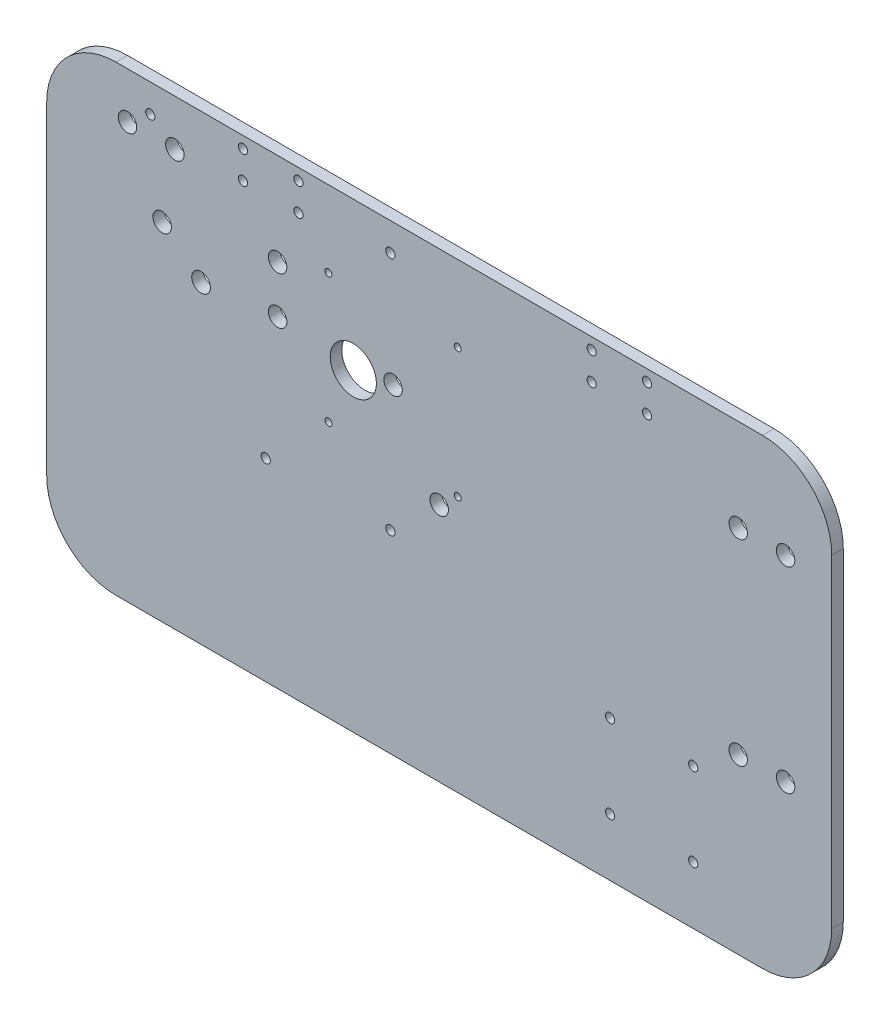
SolidWorks part; units mm, degrees
ref_plane "Alzado" through (0, 0, 0) normal (0, 0, 1) x (1, 0, 0)
ref_plane "Planta" through (0, 0, 0) normal (0, 1, 0) x (1, 0, 0)
ref_plane "Vista lateral" through (0, 0, 0) normal (1, 0, 0) x (0, 0, -1)
sketch "Croquis1" plane through (0, 0, 0) normal (0, 0, 1) x (1, 0, 0)
  line L1 (30, 0) -> (310, 0)
  line L2 (0, 30) -> (0, 170)
  line L3 (30, 200) -> (310, 200)
  line L4 (340, 30) -> (340, 170)
  arc A0 (30, 0) -> (0, 30) centre (30, 30) cw
  arc A1 (310, 0) -> (340, 30) centre (310, 30) ccw
  arc A2 (310, 200) -> (340, 170) centre (310, 170) cw
  arc A3 (0, 170) -> (30, 200) centre (30, 170) cw
  point P7 (0, 0)
  point P12 (340, 200)
  point P15 (0, 200)
  dimension "D3" = 30
  dimension "D1" = 200
  dimension "D2" = 340
extrude "Saliente-Extruir1" add sketch "Croquis1" along normal blind 5
sketch "Croquis2" plane through (0, 0, 5) normal (0, 0, -1) x (-1, 0, 0)
  line L0 (-55.5, 180) -> (-35, 180) construction
  line L2 (-310, 200) -> (-30, 200) construction
  line L3 (0, 170) -> (0, 30) construction
  line L4 (-100, 160) -> (-100, 139.5) construction
  line L5 (-310, 200) -> (-30, 200) construction
  line L6 (-299.5, 160) -> (-320, 160) construction
  line L7 (-340, 30) -> (-340, 170) construction
  line L8 (-320, 75) -> (-299.5, 75) construction
  line L9 (-30, 0) -> (-310, 0) construction
  line L10 (-100, 149.75) -> (-146.5265, 149.75) construction
  circle A0 centre (-55.5, 180) radius 4
  circle A1 centre (-35, 180) radius 4
  circle A2 centre (-100, 160) radius 4
  circle A3 centre (-100, 139.5) radius 4
  circle A4 centre (-299.5, 160) radius 4
  circle A5 centre (-320, 160) radius 4
  circle A6 centre (-320, 75) radius 4
  circle A7 centre (-299.5, 75) radius 4
  circle A8 centre (-150, 139) radius 4
  circle A9 centre (-170, 104) radius 4
  circle A10 centre (-50, 150) radius 4
  dimension "D1" = 8
  dimension "D10" = 40
  dimension "D14" = 8
  dimension "D19" = 8
  dimension "D2" = 20.5
  dimension "D3" = 35
  dimension "D4" = 20
  dimension "D5" = 20.5
  dimension "D6" = 40
  dimension "D7" = 100
  dimension "D8" = 20.5
  dimension "D9" = 20
  dimension "D11" = 20.5
  dimension "D12" = 20
  dimension "D13" = 75
  dimension "D15" = 150
  dimension "D16" = 61
  dimension "D17" = 35
  dimension "D18" = 20
  dimension "D20" = 50
  dimension "D21" = 50
extrude "Cortar-Extruir4" cut sketch "Croquis2" along normal blind 10
sketch "Croquis3" plane through (0, 0, 0) normal (0, 0, -1) x (-1, 0, 0)
  line L0 (-44.85, 187.84) -> (-148.85, 187.84) construction
  line L1 (-148.85, 187.84) -> (-148.85, 83.84) construction
  line L2 (-148.85, 83.84) -> (-94.85, 83.84) construction
  line L3 (-94.85, 83.84) -> (-44.85, 187.84) construction
  line L4 (-310, 200) -> (-30, 200) construction
  line L5 (0, 170) -> (0, 30) construction
  circle A0 centre (-148.85, 83.84) radius 2
  circle A1 centre (-94.85, 83.84) radius 2
  circle A2 centre (-44.85, 187.84) radius 2
  circle A3 centre (-148.85, 187.84) radius 2
  circle A4 centre (-132.79, 135.84) radius 10
  circle A5 centre (-66.85, 135.84) radius 4.05
  dimension "D1" = 4
  dimension "D5" = 20
  dimension "D6" = 8.1
  dimension "D2" = 104
  dimension "D3" = 104
  dimension "D4" = 54
  dimension "D7" = 16.06
  dimension "D8" = 52
  dimension "D9" = 52
  dimension "D10" = 82
  dimension "D11" = 12.16
  dimension "D12" = 66.85
extrude "Cortar-Extruir5" cut sketch "Croquis3" against normal blind 10
sketch "Croquis5" plane through (0, 0, 0) normal (0, 0, -1) x (-1, 0, 0)
  line L0 (-178, 167) -> (-122, 167) construction
  line L1 (-122, 167) -> (-122, 111) construction
  line L2 (-178, 167) -> (-178, 111) construction
  line L3 (-178, 111) -> (-122, 111) construction
  line L4 (-310, 200) -> (-30, 200) construction
  line L7 (0, 170) -> (0, 30) construction
  circle A0 centre (-178, 167) radius 1.5
  circle A1 centre (-122, 111) radius 1.5
  circle A2 centre (-122, 167) radius 1.5
  circle A3 centre (-178, 111) radius 1.5
  dimension "D1" = 3
  dimension "D4" = 3
  dimension "D2" = 56
  dimension "D3" = 56
  dimension "D5" = 33
  dimension "D6" = 122
extrude "Cortar-Extruir6" cut sketch "Croquis5" against normal blind 10
sketch "Croquis6" plane through (0, 0, 5) normal (0, 0, 1) x (1, 0, 0)
  line L0 (244, 61) -> (280, 61) construction
  line L1 (244, 61) -> (244, 25) construction
  line L2 (244, 25) -> (280, 25) construction
  line L3 (280, 25) -> (280, 61) construction
  line L4 (340, 30) -> (340, 170) construction
  line L5 (30, 0) -> (310, 0) construction
  circle A0 centre (244, 61) radius 2
  circle A1 centre (280, 61) radius 2
  circle A2 centre (244, 25) radius 2
  circle A3 centre (280, 25) radius 2
  dimension "D1" = 4
  dimension "D2" = 36
  dimension "D3" = 36
  dimension "D4" = 60
  dimension "D5" = 25
extrude "Cortar-Extruir7" cut sketch "Croquis6" against normal blind 10
sketch "Croquis7" plane through (0, 0, 5) normal (0, 0, 1) x (1, 0, 0)
  line L4 (30, 0) -> (310, 0)
  line L5 (340, 30) -> (340, 170)
  line L6 (310, 200) -> (30, 200)
  line L7 (0, 170) -> (0, 30)
  line L8 (30, 0) -> (310, 0)
  line L9 (340, 30) -> (340, 170)
  line L10 (310, 200) -> (30, 200)
  line L11 (0, 170) -> (0, 30)
  circle A0 centre (50, 150) radius 4 construction
  circle A1 centre (100, 160) radius 4 construction
  circle A2 centre (100, 139.5) radius 4 construction
  circle A3 centre (299.5, 75) radius 4 construction
  arc A4 (0, 30) -> (30, 0) centre (30, 30) ccw
  arc A5 (310, 0) -> (340, 30) centre (310, 30) ccw
  arc A6 (340, 170) -> (310, 200) centre (310, 170) ccw
  arc A7 (30, 200) -> (0, 170) centre (30, 170) ccw
  arc A8 (0, 30) -> (30, 0) centre (30, 30) ccw
  arc A9 (310, 0) -> (340, 30) centre (310, 30) ccw
  arc A10 (340, 170) -> (310, 200) centre (310, 170) ccw
  arc A11 (30, 200) -> (0, 170) centre (30, 170) ccw
  circle A12 centre (320, 75) radius 4 construction
  circle A13 centre (299.5, 160) radius 4 construction
  circle A14 centre (320, 160) radius 4 construction
  circle A15 centre (55.5, 180) radius 4 construction
  circle A16 centre (35, 180) radius 4 construction
  circle A17 centre (50, 150) radius 4
  circle A18 centre (100, 160) radius 4
  circle A19 centre (100, 139.5) radius 4
  circle A20 centre (299.5, 75) radius 4
  circle A21 centre (320, 75) radius 4
  circle A22 centre (299.5, 160) radius 4
  circle A23 centre (320, 160) radius 4
  circle A24 centre (55.5, 180) radius 4
  circle A25 centre (35, 180) radius 4
  dimension "D1" = 0
sketch "Croquis8" plane through (0, 0, 5) normal (0, 0, 1) x (1, 0, 0)
  line L0 (236, 195) -> (236, 183) construction
  line L1 (236, 195) -> (260, 195) construction
  line L2 (236, 183) -> (260, 183) construction
  line L3 (260, 183) -> (260, 195) construction
  line L4 (85, 195) -> (85, 183) construction
  line L5 (85, 195) -> (109, 195) construction
  line L6 (85, 183) -> (109, 183) construction
  line L7 (109, 183) -> (109, 195) construction
  line L8 (310, 200) -> (30, 200) construction
  line L9 (340, 30) -> (340, 170) construction
  line L10 (0, 170) -> (0, 30) construction
  circle A0 centre (236, 195) radius 2
  circle A1 centre (236, 183) radius 2
  circle A2 centre (260, 183) radius 2
  circle A3 centre (260, 195) radius 2
  circle A4 centre (85, 195) radius 2
  circle A5 centre (85, 183) radius 2
  circle A6 centre (109, 183) radius 2
  circle A7 centre (109, 195) radius 2
  dimension "D1" = 24
  dimension "D2" = 12
  dimension "D3" = 24
  dimension "D4" = 12
  dimension "D5" = 5
  dimension "D6" = 80
  dimension "D7" = 85
extrude "Cortar-Extruir8" cut sketch "Croquis8" against normal blind 10
